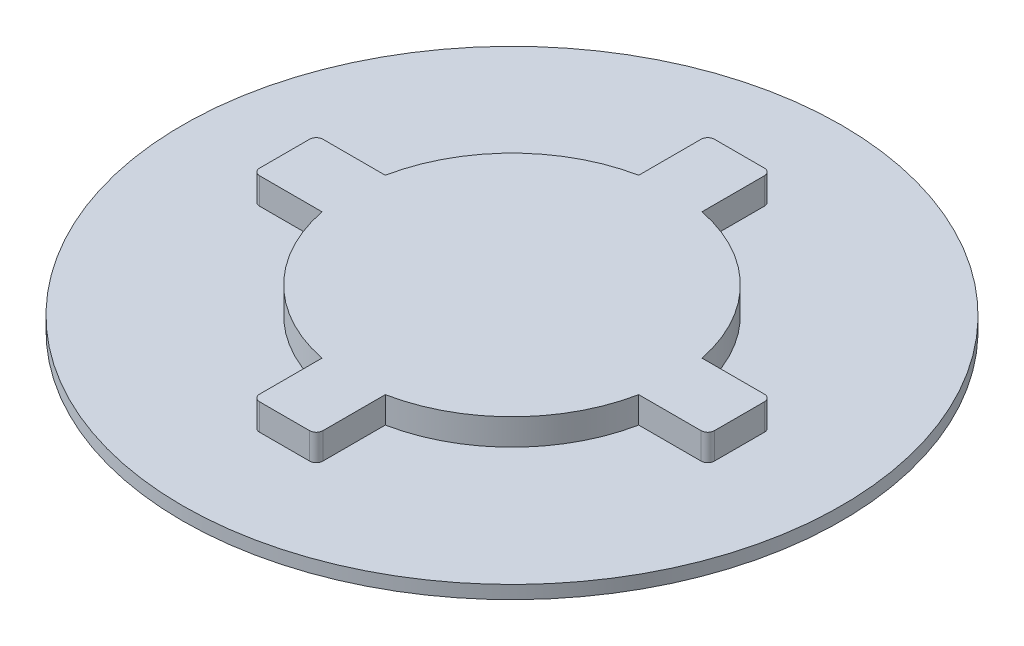
SolidWorks part; units mm, degrees
ref_plane "Alzado" through (0, 0, 0) normal (0, 0, 1) x (1, 0, 0)
ref_plane "Planta" through (0, 0, 0) normal (0, 1, 0) x (1, 0, 0)
ref_plane "Vista lateral" through (0, 0, 0) normal (1, 0, 0) x (0, 0, -1)
sketch "Croquis5" plane through (0, 0, 0) normal (0, 1, 0) x (1, 0, 0)
  circle A0 centre (0, 0) radius 24.5
  dimension "D1" = 49
extrude "Saliente-Extruir3" add sketch "Croquis5" along normal blind 4
sketch "Croquis6" plane through (0, 0, 0) normal (0, -1, 0) x (1, 0, 0)
  line L1 (33.5, 4.8) -> (-33.5, 4.8)
  line L2 (34.5, 3.8) -> (34.5, -3.8)
  line L3 (33.5, -4.8) -> (-33.5, -4.8)
  line L4 (-34.5, 3.8) -> (-34.5, -3.8)
  line L5 (34.5, 4.8) -> (-34.5, -4.8) construction
  line L6 (34.5, -4.8) -> (-34.5, 4.8) construction
  line L10 (3.8, -34.5) -> (-3.8, -34.5)
  line L11 (4.8, -33.5) -> (4.8, 33.5)
  line L12 (3.8, 34.5) -> (-3.8, 34.5)
  line L13 (-4.8, -33.5) -> (-4.8, 33.5)
  arc A0 (-3.8, -34.5) -> (-4.8, -33.5) centre (-3.8, -33.5) cw
  arc A1 (33.5, 4.8) -> (34.5, 3.8) centre (33.5, 3.8) cw
  arc A2 (34.5, -3.8) -> (33.5, -4.8) centre (33.5, -3.8) cw
  arc A3 (-33.5, -4.8) -> (-34.5, -3.8) centre (-33.5, -3.8) cw
  arc A4 (-33.5, 4.8) -> (-34.5, 3.8) centre (-33.5, 3.8) ccw
  arc A5 (4.8, -33.5) -> (3.8, -34.5) centre (3.8, -33.5) cw
  arc A6 (4.8, 33.5) -> (3.8, 34.5) centre (3.8, 33.5) ccw
  arc A7 (-4.8, 33.5) -> (-3.8, 34.5) centre (-3.8, 33.5) cw
  point P0 (0, 0)
  point P13 (0, 0)
  point P34 (0, 0)
  circle M5 centre (0, 0) radius 24.5
  dimension "D4" = 1
  dimension "D1" = 69
  dimension "D2" = 9.6
extrude "Saliente-Extruir4" add sketch "Croquis6" against normal blind 4 contours L1 L4 L3 M5 | M5 | L3 L2 L1 M5 | M5 region at (29.3987, 0, 0) region at (0, 0, 29.3987) region at (-29.3987, 0, 0) region at (0, 0, -29.3987)
sketch "Croquis7" plane through (0, 0, 0) normal (0, -1, 0) x (1, 0, 0)
  circle A0 centre (0, 0) radius 50
  dimension "D1" = 100
extrude "Saliente-Extruir5" add sketch "Croquis7" along normal blind 2
sketch "Croquis8" plane through (0, -2, 0) normal (0, -1, 0) x (1, 0, 0)
  line L0 (2.5, -25) -> (-2.5, -25)
  line L1 (25, 2.5) -> (-25, 2.5)
  line L2 (25, 2.5) -> (25, -2.5)
  line L3 (25, -2.5) -> (-25, -2.5)
  line L4 (-25, 2.5) -> (-25, -2.5)
  line L5 (25, 2.5) -> (-25, -2.5) construction
  line L6 (25, -2.5) -> (-25, 2.5) construction
  line L7 (2.5, -25) -> (2.5, 25)
  line L8 (2.5, 25) -> (-2.5, 25)
  line L9 (-2.5, -25) -> (-2.5, 25)
  circle A0 centre (0, 0) radius 15
  circle A1 centre (0, 0) radius 20
  point P0 (0, 0)
  point P13 (0, 0)
  dimension "D3" = 30
  dimension "D4" = 40
  dimension "D1" = 50
  dimension "D2" = 5
extrude "Cortar-Extruir3" cut sketch "Croquis8" against normal blind 2 contours A1 L9 L0 L7 | L9 A1 L7 A0 | L9 A0 L7 L3 | L9 L3 L7 L1 | L7 A0 L9 L1 | L7 A1 L9 A0 | A1 L7 L8 L9 | L3 A0 L1 L7 | L3 A1 L1 A0 | A1 L3 L2 L1 | L1 A0 L3 L9 | L1 A1 L3 A0 | A1 L1 L4 L3 | L9 A1 L1 A0 | L1 A1 L7 A0 | L7 A1 L3 A0 | L3 A1 L9 A0 region at (0, -2, -22.4737) region at (0, -2, -17.4389) region at (11.6344, -2, -11.6344) region at (-11.6344, -2, -11.6344) region at (0, -2, -8.7153) region at (22.4737, -2, 0) region at (17.4389, -2, 0) region at (-17.4389, -2, 0) region at (-22.4737, -2, 0) region at (8.7153, -2, 0) region at (0, -2, 0) region at (-8.7153, -2, 0) region at (-11.6344, -2, 11.6344) region at (0, -2, 8.7153) region at (11.6344, -2, 11.6344) region at (0, -2, 17.4389) region at (0, -2, 22.4737)
sketch "Croquis9" plane through (0, 0, 0) normal (0, -1, 0) x (1, 0, 0)
  line L0 (-25, 0) -> (25, 0) construction
  line L1 (-25, 2.5) -> (-25, -2.5) construction
  line L2 (25, 2.5) -> (25, -2.5) construction
  line L3 (0, -25) -> (0, 25) construction
  line L4 (2.5, -25) -> (-2.5, -25) construction
  line L5 (2.5, 25) -> (-2.5, 25) construction
  circle A0 centre (0, 0) radius 22.5 construction
  circle A1 centre (0, 0) radius 3.5355
  dimension "D1" = 45
extrude "Cortar-Extruir4" cut sketch "Croquis9" against normal blind 2.5
sketch "Croquis10" plane through (0, 0, 0) normal (0, -1, 0) x (1, 0, 0)
  line L0 (-25, 0) -> (25, 0) construction
  line L1 (-25, 2.5) -> (-25, -2.5) construction
  line L2 (25, 2.5) -> (25, -2.5) construction
  line L3 (0, 25) -> (0, -25) construction
  line L4 (2.5, 25) -> (-2.5, 25) construction
  line L5 (2.5, -25) -> (-2.5, -25) construction
  circle A0 centre (0, 0) radius 22.5 construction
  circle A1 centre (-22.5, 0) radius 0.5
  circle A2 centre (0, 22.5) radius 0.5
  circle A3 centre (22.5, 0) radius 0.5
  circle A4 centre (0, -22.5) radius 0.5
  point P26 (0, 0)
  dimension "D1" = 45
  dimension "D2" = 1
  dimension "D3" = 4
extrude "Cortar-Extruir5" cut sketch "Croquis10" against normal blind 2
